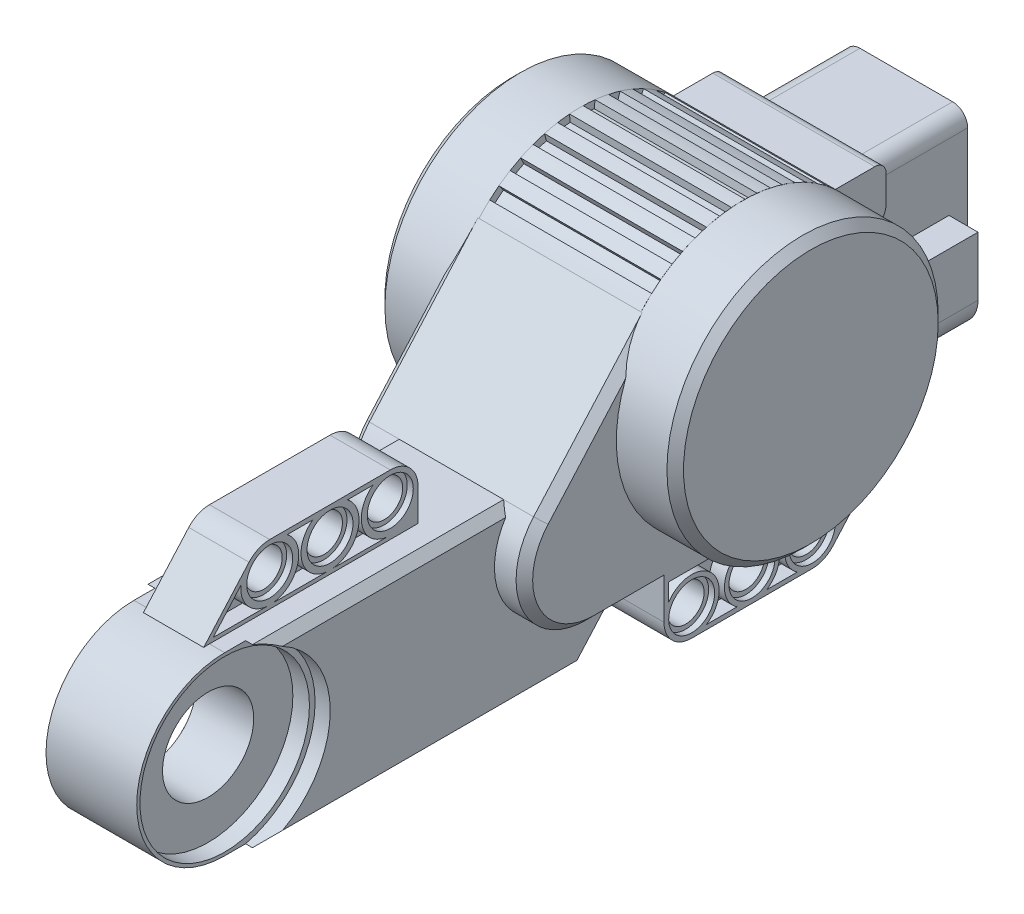
SolidWorks part; units mm, degrees
ref_plane "Front Plane" through (0, 0, 0) normal (0, 0, 1) x (1, 0, 0)
ref_plane "Top Plane" through (0, 0, 0) normal (0, 1, 0) x (1, 0, 0)
ref_plane "Right Plane" through (0, 0, 0) normal (1, 0, 0) x (0, 0, -1)
sketch "hole_outline_positions" plane through (0, 0, 0) normal (1, 0, 0) x (0, 0, -1)
  line L0 (0, 0) -> (-16, 0) construction
  line L1 (-16, 0) -> (-16, 24) construction
  line L2 (-16, 24) -> (-64, 24) construction
  line L3 (0, 0) -> (12, 8) construction
  line L4 (-64, 24) -> (-64, 8) construction
  line L5 (-64, 8) -> (-72, 8) construction
  dimension "D1" = 16
  dimension "D2" = 24
  dimension "D3" = 48
  dimension "D4" = 12
  dimension "D5" = 8
  dimension "D6" = 16
  dimension "D7" = 8
sketch "axle_point" plane through (0, 0, 0) normal (1, 0, 0) x (0, 0, -1)
  point P0 (-72, 8)
sketch "Sketch3" plane through (0, 0, 0) normal (1, 0, 0) x (0, 0, -1)
  line L0 (-8, 24) -> (-8, 0) construction
  line L1 (0, 0) -> (-16, 0) construction
  circle A0 centre (-8, 24) radius 18
  dimension "motor_body_diam" = 36
  dimension "motor_body_height_loc" = 24
extrude "motor_body" add sketch "Sketch3" along normal mid plane 39.63
sketch "Sketch4" plane through (0, 0, 0) normal (1, 0, 0) x (0, 0, -1)
  line L0 (-64, 27.675) -> (-48, 27.675)
  line L1 (-16, 24) -> (-64, 24) construction
  line L2 (-66.7504, 26.4374) -> (-76, 16)
  line L3 (-44.325, 24) -> (-44.325, 16)
  line L4 (-44.325, 16) -> (-76, 16)
  arc A0 (-48, 27.675) -> (-44.325, 24) centre (-48, 24) cw
  arc A1 (-66.7504, 26.4374) -> (-64, 27.675) centre (-64, 24) cw
  circle A2 centre (-64, 24) radius 2.45
  circle A3 centre (-56, 24) radius 2.45
  circle A4 centre (-48, 24) radius 2.45
  dimension "D3" = 8
  dimension "top_frnt_tab_bkrad" = 3.675
  dimension "D2" = 3.675
  dimension "top_peg_tab_Langle" = 12
  dimension "peg_hole_diam" = 4.9
extrude "front_top_peg_tab" add sketch "Sketch4" along normal mid plane 8 separate body
sketch "Sketch5" plane through (4, 0, 0) normal (1, 0, 0) x (0, 0, -1)
  circle A0 centre (-64, 24) radius 3.05
  circle A1 centre (-64, 24) radius 2.45 construction
  dimension "cntr_bore_diam" = 6.1
extrude "peg_counterbore_cut" cut sketch "Sketch5" against normal blind 0.8
pattern_linear "peg_counterbore_lin_pattern" count 3 spacing 8 along (0, 0, -1) of "peg_counterbore_cut"
mirror "peg_counterbore_mirror" about plane through (0, 0, 0) normal (1, 0, 0) of "peg_counterbore_lin_pattern", "peg_counterbore_cut"
move or copy body "Body-Move/Copy1" bodies to move or copy 105 copy yes number of copies 1 translate (0, 0, -64)
sketch "Sketch6" plane through (0, 0, 0) normal (1, 0, 0) x (0, 0, -1)
  circle A0 centre (0, 24) radius 2.45 construction
  point P0 (0, 24)
move or copy body "Body-Move/Copy2" bodies to move or copy 106 copy no rotation origin (0, 24, 0) rotation axis (1, 0, 0) rotation angle 180
move or copy body "Body-Move/Copy3" bodies to move or copy 107 copy no translate (0, -24, 0)
move or copy body "Body-Move/Copy4" bodies to move or copy 108 copy no translate (8, 0, 0)
mirror "Mirror2" about plane through (0, 0, 0) normal (1, 0, 0) of bodies 109
ref_plane "back_pegholes_plane" through (0, 0, -12) normal (0, 0, 1) x (1, 0, 0)
sketch "Sketch9" plane through (0, 8, 0) normal (0, 1, 0) x (-1, 0, 0)
  line L1 (-12, 19.675) -> (12, 19.675)
  line L2 (-12, 19.675) -> (-12, -12)
  line L3 (-12, -12) -> (12, -12)
  line L4 (12, 19.675) -> (12, -12)
extrude "bottom_peg_base_ext" add sketch "Sketch9" along normal up to vertex (16 mm away) separate body up to point (0, 24, 16)
sketch "Sketch8" plane through (0, 0, -12) normal (0, 0, 1) x (1, 0, 0)
  line L0 (8, 8) -> (-8, 8) construction
  line L1 (8, 11.675) -> (-8, 11.675)
  line L2 (8, 4.325) -> (-8, 4.325)
  arc A3 (8, 4.325) -> (8, 11.675) centre (8, 8) ccw
  arc A4 (-8, 4.325) -> (-8, 11.675) centre (-8, 8) cw
  dimension "back_peg_hole_length" = 16
  dimension "peg_body_top_width" = 7.35
extrude "bk_peg_body_hole_cut" cut sketch "Sketch8" along normal blind 10
sketch "Sketch11" plane through (0, 0, 0) normal (0, 0, 1) x (1, 0, 0)
  line L0 (8, 8) -> (-8, 8) construction
  line L1 (8, 11.675) -> (-8, 11.675)
  line L2 (8, 4.325) -> (-8, 4.325)
  arc A3 (8, 4.325) -> (8, 11.675) centre (8, 8) ccw
  arc A4 (-8, 4.325) -> (-8, 11.675) centre (-8, 8) cw
  dimension "back_peg_hole_length" = 16
  dimension "peg_body_top_width" = 7.35
extrude "back_peg_holes_body" add sketch "Sketch11" along normal up to vertex and the other way up to vertex separate body
sketch "Sketch12" plane through (0, 0, -12) normal (0, 0, 1) x (1, 0, 0)
  circle A0 centre (0, 8) radius 2.45
  circle A1 centre (-8, 8) radius 2.45
  circle A2 centre (8, 8) radius 2.45
  dimension "peg_hole_diam" = 4.9
extrude "back_peg_holes_cut" cut sketch "Sketch12" along normal blind 8
sketch "Sketch13" plane through (0, 0, 0) normal (1, 0, 0) x (0, 0, -1)
  line L0 (-16, -3.675) -> (0, -3.675) construction
  line L1 (-72, 19.675) -> (-19.675, 19.675)
  line L2 (-19.675, 24) -> (-19.675, 8) construction
  line L3 (-19.675, 4.325) -> (-26.7646, -3.675)
  line L4 (-72, -3.675) -> (-26.7646, -3.675)
  line L5 (-19.675, 19.675) -> (-19.675, 4.325)
  arc A0 (-72, 19.675) -> (-72, -3.675) centre (-72, 8) ccw
  dimension "D1" = 48.453
extrude "front_arm_body" add sketch "Sketch13" along normal mid plane 16.06 separate body
sketch "Sketch14" plane through (8.03, 0, 0) normal (1, 0, 0) x (0, 0, -1)
  circle A0 centre (-72, 8) radius 12
  dimension "D1" = 24
extrude "l_wheel_recess" cut sketch "Sketch14" against normal blind 2.01
mirror "r_wheel_recess_mirror" about plane through (0, 0, 0) normal (1, 0, 0) of "l_wheel_recess"
sketch "Sketch15" plane through (0, 0, 0) normal (1, 0, 0) x (0, 0, -1)
  line L0 (-19.675, 4.325) -> (-28.9768, 4.325)
  line L1 (-35.8838, 19.675) -> (-21.4714, 35.9383)
  line L2 (-21.4714, 35.9383) -> (-5.2753, 4.325)
  line L3 (-19.675, 4.325) -> (12, 4.325) construction
  line L4 (-5.2753, 4.325) -> (-19.675, 4.325)
  line L5 (-19.675, 19.675) -> (-69.2261, 19.675) construction
  arc A0 (-28.9768, 4.325) -> (-35.8838, 19.675) centre (-28.9768, 13.554) cw
  circle A1 centre (-8, 24) radius 18 construction
  dimension "D1" = 48.453
extrude "angled_midfront_body" add sketch "Sketch15" along normal mid plane 24 separate body
sketch "Sketch16" plane through (0, 0, -12) normal (0, 0, 1) x (1, 0, 0)
  circle A0 centre (8, 8) radius 3.05
  circle A1 centre (8, 8) radius 2.45 construction
  dimension "cntr_bore_diam" = 6.1
extrude "back_peg_hole_cntrbore" cut sketch "Sketch16" along normal blind 0.8
pattern_linear "back_peg_hole_cntrbore_pattern" count 3 spacing 8 along (-1, 0, 0) of "back_peg_hole_cntrbore"
chamfer "Chamfer6" distance 1.1 angle 45 6 edges at (12, 4.325, 17.126) (12, 9.7669, 37.393) (12, 27.8066, 28.6776) (-12, 4.325, 17.126) (-12, 9.7669, 37.393) (-12, 27.8066, 28.6776)
combine bodies "Combine1" operation type add bodies to combine 105 122
combine bodies "Combine2" operation type add bodies to combine 126 123 113 114 115 116
sketch "Sketch17" plane through (0, 0, -12) normal (0, 0, -1) x (-1, 0, 0)
  line L0 (-8, 12.175) -> (8, 12.175)
  line L1 (12, 24) -> (12, 8) construction
  line L2 (12, 16.175) -> (12, 24)
  line L3 (12, 24) -> (-12, 24)
  line L4 (-12, 24) -> (-12, 16.175)
  line L5 (-12, 24) -> (-12, 8) construction
  line L6 (-8, 11.675) -> (8, 11.675) construction
  arc A0 (8, 12.175) -> (12, 16.175) centre (8, 16.175) ccw
  arc A1 (-12, 16.175) -> (-8, 12.175) centre (-8, 16.175) ccw
  dimension "D2" = 4
  dimension "D1" = 0.5
extrude "Extrude1" add sketch "Sketch17" along normal blind 10
ref_plane "jack_plane" through (0, 0, -24.48) normal (0, 0, -1) x (-1, 0, 0)
sketch "Sketch18" plane through (0, 0, -24.48) normal (0, 0, -1) x (-1, 0, 0)
  line L0 (-8.15, 16.175) -> (8.15, 16.175)
  line L1 (8.15, 16.175) -> (8.15, 34.825)
  line L2 (8.15, 34.825) -> (-8.15, 34.825)
  line L3 (-8.15, 34.825) -> (-8.15, 16.175)
  line L4 (-8.15, 0) -> (8.15, 0) construction
  line L5 (-8, 12.175) -> (8, 12.175) construction
  dimension "D1" = 16.3
  dimension "D2" = 18.65
  dimension "D3" = 4
extrude "jack_body" add sketch "Sketch18" against normal blind 45 separate body
fillet "jack_fillet" radius 2 4 edges at (-8.15, 34.825, -1.98) (-8.15, 16.175, -1.98) (8.15, 16.175, -1.98) (8.15, 34.825, -1.98)
sketch "Sketch20" plane through (0, 24, 0) normal (0, 1, 0) x (-1, 0, 0)
  line L0 (-12, -10) -> (12, -10) construction
  line L1 (10.75, -10) -> (-10.75, -10)
  line L2 (10.75, -10) -> (10.75, 21.4714)
  line L3 (10.75, 21.4714) -> (-10.75, 21.4714)
  line L4 (-10.75, -10) -> (-10.75, 21.4714)
  line L5 (-10.9, 21.4714) -> (10.9, 21.4714) construction
  line L6 (0, -10) -> (0, 21.4714) construction
  dimension "D1" = 21.5
extrude "Cut-Extrude1" cut sketch "Sketch20" along normal through all
sketch "Sketch21" plane through (0, 0, 0) normal (1, 0, 0) x (0, 0, -1)
  line L0 (-21.4714, 24) -> (-21.4714, 35.9383)
  line L1 (4.3127, 37.13) -> (9.55, 37.13)
  line L2 (10, 24) -> (22, 24) construction
  line L3 (11.05, 35.63) -> (11.05, 32.0624)
  line L4 (-21.4714, 24) -> (9.0493, 24)
  line L6 (24.48, 32.825) -> (24.48, 18.175) construction
  line L7 (9.0493, 24) -> (9.0493, 29.7726)
  line L8 (-19.3936, 36.6169) -> (-20.0638, 37.3591)
  line L9 (-18.237, 37.5721) -> (-18.8392, 38.3705)
  line L10 (-13.9549, 39.9229) -> (-14.3052, 40.8595)
  line L11 (-12.5281, 40.3858) -> (-12.7945, 41.3497)
  line L12 (-10.869, 40.7562) -> (-11.0377, 41.7418)
  line L13 (-9.3807, 40.9438) -> (-9.462, 41.9405)
  line L14 (-7.6816, 40.997) -> (-7.6629, 41.9968)
  line L15 (-6.1845, 40.9028) -> (-6.0778, 41.8971)
  line L16 (-4.5055, 40.637) -> (-4.2999, 41.6156)
  line L17 (-3.0525, 40.2641) -> (-2.7615, 41.2209)
  line L18 (-1.4529, 39.6887) -> (-1.0678, 40.6116)
  line L19 (-0.0954, 39.0505) -> (0.3696, 39.9358)
  line L20 (1.3682, 38.1858) -> (1.9193, 39.0202)
  line L21 (2.5822, 37.3048) -> (3.2047, 38.0874)
  line L23 (-16.8303, 38.5267) -> (-17.3498, 39.3812)
  line L24 (-15.5154, 39.2485) -> (-15.9575, 40.1455)
  circle A0 centre (-8, 24) radius 18 construction
  arc A1 (4.3127, 37.13) -> (3.2047, 38.0874) centre (-8, 24) ccw
  arc A2 (9.55, 37.13) -> (11.05, 35.63) centre (9.55, 35.63) cw
  arc A3 (9.0493, 29.7726) -> (11.05, 32.0624) centre (8.7393, 32.0624) ccw
  arc A4 (-12.5281, 40.3858) -> (-13.9549, 39.9229) centre (-8, 24) ccw
  arc A5 (-20.0638, 37.3591) -> (-21.4714, 35.9383) centre (-8, 24) ccw
  arc A6 (-14.3052, 40.8595) -> (-15.9575, 40.1455) centre (-8, 24) ccw
  arc A7 (-11.0377, 41.7418) -> (-12.7945, 41.3497) centre (-8, 24) ccw
  arc A8 (-7.6629, 41.9968) -> (-9.462, 41.9405) centre (-8, 24) ccw
  arc A9 (-4.2999, 41.6156) -> (-6.0778, 41.8971) centre (-8, 24) ccw
  arc A10 (-1.0678, 40.6116) -> (-2.7615, 41.2209) centre (-8, 24) ccw
  arc A11 (1.9193, 39.0202) -> (0.3696, 39.9358) centre (-8, 24) ccw
  arc A12 (-17.3498, 39.3812) -> (-18.8392, 38.3705) centre (-8, 24) ccw
  arc A13 (-15.5154, 39.2485) -> (-16.8303, 38.5267) centre (-8, 24) ccw
  arc A14 (-18.237, 37.5721) -> (-19.3936, 36.6169) centre (-8, 24) ccw
  arc A16 (-9.3807, 40.9438) -> (-10.869, 40.7562) centre (-8, 24) ccw
  arc A17 (-6.1845, 40.9028) -> (-7.6816, 40.997) centre (-8, 24) ccw
  arc A18 (-3.0525, 40.2641) -> (-4.5055, 40.637) centre (-8, 24) ccw
  arc A19 (-0.0954, 39.0505) -> (-1.4529, 39.6887) centre (-8, 24) ccw
  arc A20 (2.5822, 37.3048) -> (1.3682, 38.1858) centre (-8, 24) ccw
  dimension "D4" = 1.5
  dimension "D2" = 1
  dimension "D1" = 13.13
  dimension "D3" = 13.43
  dimension "D5" = 2
extrude "Extrude2" add sketch "Sketch21" along normal mid plane 21.5 separate body
combine bodies "Combine3" operation type add bodies to combine 133 129
sketch "Sketch23" plane through (0, 0, -24.48) normal (0, 0, -1) x (-1, 0, 0)
  line L0 (-5.55, 17.975) -> (-5.55, 32.225)
  line L1 (-5.55, 32.225) -> (5.55, 32.225)
  line L2 (5.55, 32.225) -> (5.55, 17.975)
  line L3 (-5.55, 17.975) -> (5.55, 17.975)
  line L4 (-6.15, 16.175) -> (6.15, 16.175) construction
  line L5 (8.15, 18.175) -> (8.15, 32.825) construction
  line L6 (-8.15, 32.825) -> (-8.15, 18.175) construction
  line L7 (6.15, 34.825) -> (-6.15, 34.825) construction
  dimension "D1" = 1.8
  dimension "D2" = 2.6
  dimension "D3" = 2.6
  dimension "D4" = 2.6
sketch "Sketch22" plane through (0, 0, -24.48) normal (0, 0, -1) x (-1, 0, 0)
  line L0 (-4.925, 17.975) -> (4.925, 17.975)
  line L1 (4.925, 17.975) -> (4.925, 28.265)
  line L2 (4.925, 28.265) -> (3.79, 28.265)
  line L3 (3.79, 28.265) -> (3.79, 31.875)
  line L4 (3.79, 31.875) -> (0.49, 31.875)
  line L5 (0.49, 31.875) -> (0.49, 28.265)
  line L6 (0.49, 28.265) -> (-0.645, 28.265)
  line L7 (-0.645, 28.265) -> (-0.645, 26.765)
  line L8 (-0.645, 26.765) -> (-4.925, 26.765)
  line L9 (-4.925, 26.765) -> (-4.925, 17.975)
  line L11 (-6.15, 16.175) -> (6.15, 16.175) construction
  line L12 (0, 17.975) -> (0, 28.265) construction
  dimension "D1" = 3.3
  dimension "D2" = 9.85
  dimension "D3" = 5.57
  dimension "D4" = 10.29
  dimension "D5" = 13.9
  dimension "D6" = 1.5
  dimension "D7" = 1.8
extrude "Cut-Extrude2" cut sketch "Sketch23" against normal blind 12.5
sketch "Sketch25" plane through (0, 0, -11.98) normal (0, 0, -1) x (-1, 0, 0)
  line L0 (-5.55, 17.975) -> (5.55, 17.975) construction
  line L1 (5.55, 17.975) -> (-5.55, 17.975)
  line L2 (5.55, 17.975) -> (5.55, 32.225)
  line L3 (5.55, 32.225) -> (-5.55, 32.225)
  line L4 (-5.55, 17.975) -> (-5.55, 32.225)
  line L5 (5.55, 17.975) -> (5.55, 24) construction
extrude "Extrude5" add sketch "Sketch25" along normal blind 12.5 separate body
extrude "Cut-Extrude3" cut sketch "Sketch22" against normal blind 2.3
sketch "Sketch26" plane through (0, 0, -22.18) normal (0, 0, -1) x (-1, 0, 0)
  line L0 (-4.925, 21.175) -> (4.925, 21.175)
  line L1 (-4.925, 26.765) -> (-4.925, 17.975) construction
  line L2 (4.925, 17.975) -> (4.925, 28.265) construction
  line L3 (4.925, 21.175) -> (4.925, 28.265)
  line L4 (4.925, 28.265) -> (3.79, 28.265)
  line L5 (3.79, 28.265) -> (3.79, 31.875)
  line L6 (3.79, 31.875) -> (0.49, 31.875)
  line L7 (0.49, 31.875) -> (0.49, 28.265)
  line L8 (0.49, 28.265) -> (-0.645, 28.265)
  line L9 (-0.645, 28.265) -> (-0.645, 26.765)
  line L10 (-0.645, 26.765) -> (-4.925, 26.765)
  line L11 (-4.925, 26.765) -> (-4.925, 21.175)
  line L13 (-5.55, 17.975) -> (5.55, 17.975) construction
  dimension "D1" = 3.2
extrude "Cut-Extrude4" cut sketch "Sketch26" against normal blind 9.9
sketch "Sketch27" plane through (0, 0, -22.18) normal (0, 0, -1) x (-1, 0, 0)
  line L0 (-3, 21.175) -> (-3, 18.675)
  line L1 (-4.925, 21.175) -> (4.925, 21.175) construction
  line L2 (-3, 18.675) -> (3, 18.675)
  line L3 (3, 18.675) -> (3, 21.175)
  line L4 (3, 21.175) -> (4.925, 21.175) construction
  line L5 (-3, 21.175) -> (-4.925, 21.175) construction
  line L6 (-3, 21.175) -> (3, 21.175)
  dimension "D1" = 6
  dimension "D2" = 2.5
extrude "Cut-Extrude5" cut sketch "Sketch27" against normal blind 3
chamfer "Chamfer7" distance 1.1 angle 45 2 edges at (-19.815, 24, -10) (19.815, 24, -10)
chamfer "Chamfer8" distance 1.1 angle 45 6 edges at (-8.03, 0.325, 23.2198) (-8.03, -3.675, 47.9954) (8.03, 0.325, 23.2198) (8.03, -3.675, 47.9954) (-8.03, 19.675, 52.555) (8.03, 19.675, 52.555)
sketch "Sketch28" plane through (4, 0, 0) normal (1, 0, 0) x (0, 0, -1)
  line L0 (-58.3167, 27.075) -> (-61.6833, 27.075)
  line L1 (-56.438, 20.175) -> (-63.562, 20.175)
  line L2 (-64.438, 20.175) -> (-71.4984, 20.175)
  line L3 (-48.438, 20.175) -> (-55.562, 20.175)
  line L7 (-66.3014, 26.0395) -> (-72.3164, 19.2519)
  line L8 (-67.8378, 24.3057) -> (-71.4984, 20.175)
  line L10 (-48, 27.075) -> (-64, 27.075)
  line L11 (-50.3167, 27.075) -> (-53.6833, 27.075)
  arc A0 (-55.562, 20.175) -> (-53.6833, 27.075) centre (-56, 24) ccw
  arc A1 (-63.562, 20.175) -> (-61.6833, 27.075) centre (-64, 24) ccw
  circle A2 centre (-64, 24) radius 3.85
  arc A3 (-67.8378, 24.3057) -> (-64.438, 20.175) centre (-64, 24) ccw
  circle A5 centre (-56, 24) radius 3.85
  arc A6 (-58.3167, 27.075) -> (-56.438, 20.175) centre (-56, 24) ccw
  circle A8 centre (-48, 24) radius 3.85
  arc A9 (-50.3167, 27.075) -> (-48.438, 20.175) centre (-48, 24) ccw
  dimension "D1" = 0.6
  dimension "D2" = 0.6
  dimension "D5" = 0.8
  dimension "D6" = 0.8
  dimension "D7" = 0.8
extrude "Cut-Extrude6" cut sketch "Sketch28" against normal blind 2
mirror "Mirror3" about plane through (0, 0, 0) normal (1, 0, 0) of "Cut-Extrude6"
sketch "Sketch29" plane through (12, 0, 0) normal (1, 0, 0) x (0, 0, -1)
  line L0 (-19.075, 4.325) -> (7.6743, 4.325)
  line L1 (-19.675, 4.325) -> (-28.9768, 4.325) construction
  line L4 (2.1517, -1.9068) -> (11.4013, 8.5306)
  line L5 (3.6431, -0.2238) -> (7.6743, 4.325)
  line L7 (-19.075, 5.425) -> (-19.075, 0)
  line L8 (-19.075, 4.325) -> (-19.075, 1.9664)
  line L9 (-6.0336, -3.075) -> (-1.9664, -3.075)
  line L10 (-16, -3.075) -> (0, -3.075)
  line L11 (-14.0336, -3.075) -> (-9.9664, -3.075)
  circle A2 centre (0, 0) radius 3.65
  arc A3 (3.6431, -0.2238) -> (-1.9664, -3.075) centre (0, 0) ccw
  circle A5 centre (-8, 0) radius 3.65
  arc A6 (-6.0336, -3.075) -> (-9.9664, -3.075) centre (-8, 0) ccw
  circle A8 centre (-16, 0) radius 3.65
  arc A9 (-14.0336, -3.075) -> (-19.075, 1.9664) centre (-16, 0) ccw
  dimension "D1" = 0.8
  dimension "D2" = 0.6
  dimension "D3" = 0.6
  dimension "D4" = 0.6
  dimension "D5" = 0.6
  dimension "D6" = 0.6
extrude "Cut-Extrude7" cut sketch "Sketch29" against normal blind 2
mirror "Mirror4" about plane through (0, 0, 0) normal (1, 0, 0) of "Cut-Extrude7"
ref_plane "Plane1" through (8.075, 0, 0) normal (1, 0, 0) x (0, 0, -1)
mirror "Mirror6" about plane through (8.075, 0, 0) normal (1, 0, 0) of "Cut-Extrude7"
mirror "Mirror7" about plane through (0, 0, 0) normal (1, 0, 0) of "Mirror6"
sketch "Sketch31" plane through (0, 0, -12) normal (0, 0, 1) x (1, 0, 0)
  line L2 (8, 10.875) -> (-8, 10.875)
  line L3 (5.7513, 10.875) -> (2.2487, 10.875)
  line L4 (2.2487, 5.125) -> (5.7513, 5.125)
  line L5 (-8, 5.125) -> (8, 5.125)
  line L6 (-5.7513, 5.125) -> (-2.2487, 5.125)
  line L7 (-2.2487, 10.875) -> (-5.7513, 10.875)
  circle A2 centre (8, 8) radius 3.65
  arc A3 (5.7513, 10.875) -> (5.7513, 5.125) centre (8, 8) ccw
  circle A5 centre (0, 8) radius 3.65
  arc A6 (2.2487, 5.125) -> (2.2487, 10.875) centre (0, 8) ccw
  arc A7 (-2.2487, 10.875) -> (-2.2487, 5.125) centre (0, 8) ccw
  circle A8 centre (-8, 8) radius 3.65
  arc A9 (-5.7513, 5.125) -> (-5.7513, 10.875) centre (-8, 8) ccw
  dimension "D1" = 0.8
  dimension "D2" = 0.8
  dimension "D3" = 0.6
  dimension "D4" = 0.6
  dimension "D5" = 0.6
extrude "Cut-Extrude10" cut sketch "Sketch31" along normal blind 2
sketch "Sketch32" plane through (6.02, 0, 0) normal (1, 0, 0) x (0, 0, -1)
  circle A0 centre (-72, 8) radius 6.05
  dimension "D1" = 12.1
extrude "Cut-Extrude11" cut sketch "Sketch32" against normal through all
sketch "Sketch34" plane through (6.02, 0, 0) normal (1, 0, 0) x (0, 0, -1)
  circle A0 centre (-72, 8) radius 11.25
  circle A1 centre (-72, 8) radius 6.05 construction
  dimension "D1" = 22.5
extrude "Cut-Extrude12" cut sketch "Sketch34" against normal blind 2.2
mirror "Mirror8" about plane through (0, 0, 0) normal (1, 0, 0) of "Cut-Extrude12"
ref_plane "inner_right_mate_plane" through (3.2, 0, 0) normal (1, 0, 0) x (0, 0, -1)
ref_plane "inner_left_mate_plane" through (-3.2, 0, 0) normal (-1, 0, 0) x (0, 0, 1)
ref_plane "outer_right_mate_plane" through (11.2, 0, 0) normal (1, 0, 0) x (0, 0, -1)
ref_plane "outer_left_mate_plane" through (-11.2, 0, 0) normal (-1, 0, 0) x (0, 0, 1)
ref_plane "back_mate_plane" through (0, 0, -11.2) normal (0, 0, -1) x (-1, 0, 0)
sketch "Sketch35" plane through (0, 4.325, 0) normal (0, -1, 0) x (1, 0, 0)
  line L0 (-4, 16) -> (-4, 0) construction
  line L1 (4, 16) -> (4, 0) construction
  line L2 (-8, 19.675) -> (8, 19.675) construction
  line L3 (-12, -2.7504) -> (-4, -2.7504) construction
  line L8 (-4, 19.675) -> (-4, -2.7504)
  line L9 (-4, -2.7504) -> (4, -2.7504)
  line L10 (4, -2.7504) -> (4, 19.675)
  line L11 (4, 19.675) -> (-4, 19.675)
extrude "Extrude8" add sketch "Sketch35" along normal blind 0.01 separate body
equation "\"D1@Sketch13\" = \"RD1@Annotations\""
equation "\"D1@Sketch15\" = \"RD1@Annotations\""
